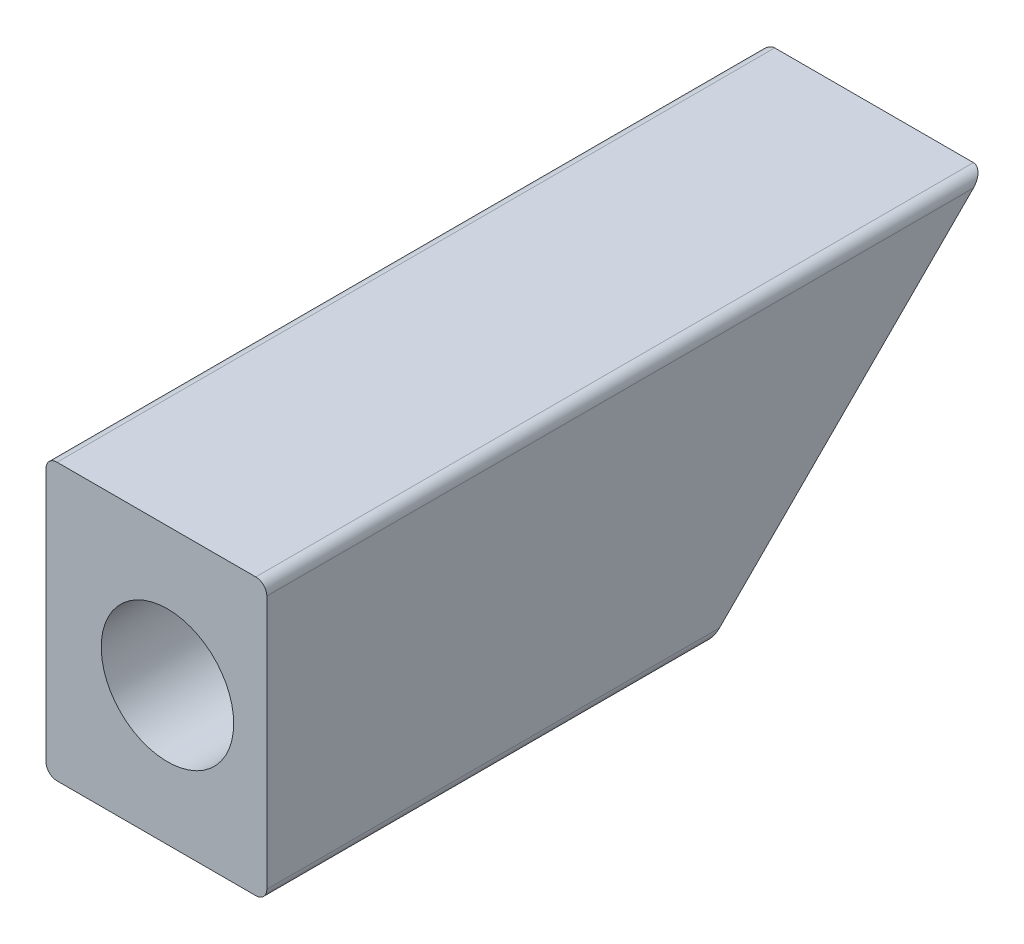
SolidWorks part; units mm, degrees
ref_plane "前视基准面" through (0, 0, 0) normal (0, 0, 1) x (1, 0, 0)
ref_plane "上视基准面" through (0, 0, 0) normal (0, 1, 0) x (1, 0, 0)
ref_plane "右视基准面" through (0, 0, 0) normal (1, 0, 0) x (0, 0, -1)
other "Configuration Table"
sketch "Sketch1" plane through (0, 0, 0) normal (1, 0, 0) x (0, 0, -1)
  line L0 (20, -12.5) -> (45, 12.5)
  line L1 (-20, -12.5) -> (20, -12.5)
  line L2 (-20, -12.5) -> (-20, 12.5)
  line L3 (-20, 12.5) -> (20, 12.5)
  line L4 (20, -12.5) -> (20, 12.5)
  line L5 (-20, -12.5) -> (20, 12.5) construction
  line L6 (-20, 12.5) -> (20, -12.5) construction
  line L7 (20, 12.5) -> (45, 12.5)
  point P0 (0, 0)
  dimension "D1" = 25
  dimension "D2" = 40
  dimension "D3" = 45
extrude "Boss-Extrude1" add sketch "Sketch1" along normal blind 20 contours L7 L4 L0 | L1 L4 L3 L2 region at (0, 4.1667, -28.3333) region at (0, 0, 0)
sketch "Sketch2" plane through (0, 0, 0) normal (0, 0, 1) x (1, 0, 0)
  line L0 (10, 12.5) -> (10, -12.5) construction
  line L1 (20, 12.5) -> (0, 12.5) construction
  line L2 (20, -12.5) -> (0, -12.5) construction
  line L3 (0, 0) -> (20, 0) construction
  line L4 (20, -12.5) -> (20, 12.5) construction
  circle A0 centre (11, 0) radius 6
  dimension "D1" = 9
extrude "Cut-Extrude1" cut sketch "Sketch2" against normal blind 67 and the other way blind 43
fillet "Fillet1" radius 1 4 edges at (0, 12.5, -12.5) (0, -12.5, 0) (20, -12.5, 0) (20, 12.5, -12.5)
sketch "Sketch4" plane through (0, 0, 0) normal (-1, 0, 0) x (0, 0, 1)
  circle A0 centre (0, 0) radius 11
extrude "Cut-Extrude2" cut sketch "Sketch4" against normal blind 2
